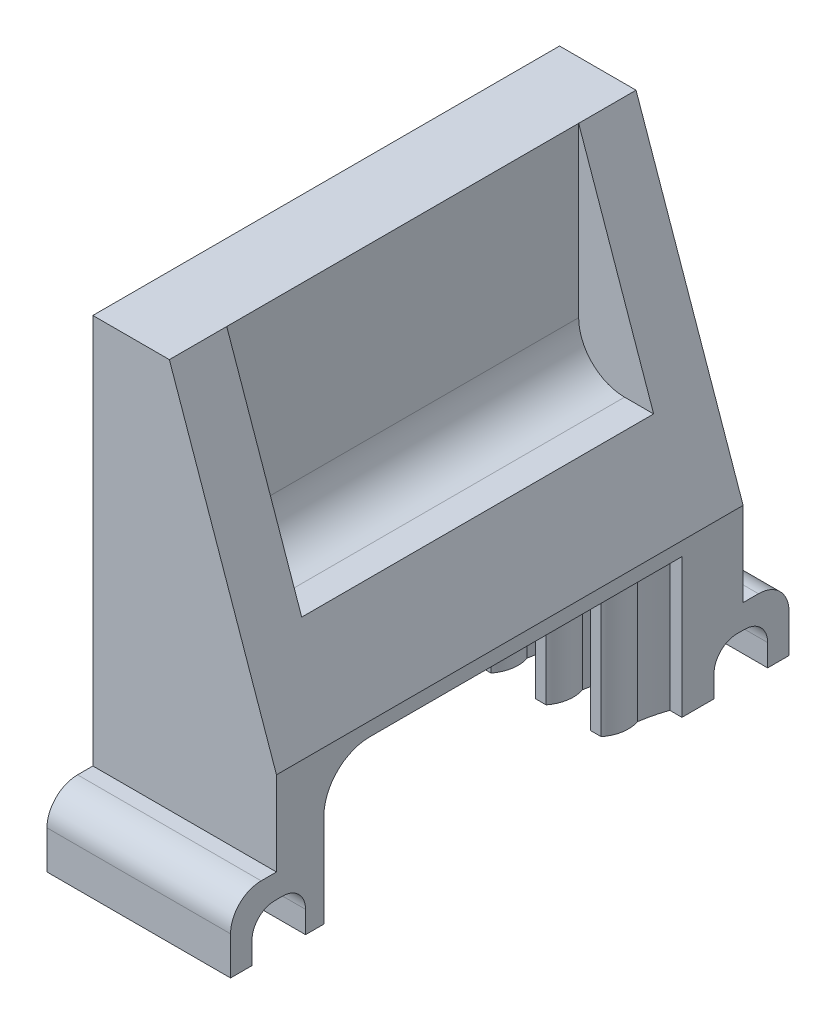
SolidWorks part; units mm, degrees
ref_plane "Front Plane" through (0, 0, 0) normal (0, 0, 1) x (1, 0, 0)
ref_plane "Top Plane" through (0, 0, 0) normal (0, 1, 0) x (1, 0, 0)
ref_plane "Right Plane" through (0, 0, 0) normal (1, 0, 0) x (0, 0, -1)
sketch "Sketch1" plane through (0, 0, 0) normal (0, 0, 1) x (1, 0, 0)
  line L0 (0, 0) -> (0, -30)
  line L1 (0, -30) -> (12, -30)
  line L2 (12, -30) -> (12, -20)
  line L3 (12, -20) -> (5, 0)
  line L4 (5, 0) -> (0, 0)
  dimension "D1" = 30
  dimension "D2" = 12
  dimension "D3" = 10
  dimension "D4" = 5
extrude "Boss-Extrude1" add sketch "Sketch1" against normal blind 30.5
sketch "Sketch4" plane through (0, 0, 0) normal (-1, 0, 0) x (0, 0, 1)
  line L0 (-30.5, 0) -> (-30.5, -30) construction
  line L1 (-26.5, -20.8999) -> (-3.1, -20.8999)
  line L2 (-26.5, -20.8999) -> (-26.5, -30.8999)
  line L3 (-26.5, -30.8999) -> (-3.1, -30.8999)
  line L4 (-3.1, -20.8999) -> (-3.1, -30.8999)
  point P4 (-26.5, -25.8999)
  dimension "D1" = 23.4
  dimension "D2" = 10
  dimension "D3" = 4
extrude "Cut-Extrude2" cut sketch "Sketch4" against normal blind 25 contours L2 L1 L4 L3
ref_plane "Plane1" through (0, 0, -15.25) normal (0, 0, 1) x (1, 0, 0)
sketch "Sketch6" plane through (0, 0, -15.25) normal (0, 0, 1) x (1, 0, 0)
  line L0 (5, 0) -> (5, -14)
  line L1 (5, -14) -> (9.9, -14)
  line L2 (12, -20) -> (5, 0) construction
  line L3 (9.9, -14) -> (5, 0)
  dimension "D1" = 14
extrude "Cut-Extrude4" cut sketch "Sketch6" against normal mid plane 23
ref_plane "Plane2" through (0, -26.4, 0) normal (0, 1, 0) x (1, 0, 0)
ref_plane "Plane3" through (0, -30, 0) normal (0, 1, 0) x (1, 0, 0)
sketch "Sketch7" plane through (0, -30, 0) normal (0, 1, 0) x (1, 0, 0)
  line L0 (11.2768, 28.75) -> (-19.7232, 28.75)
  line L62 (-6.6, 15.25) -> (6.6, 15.25) construction
  line L162 (11.2768, 28.75) -> (11.2768, 27.05)
  line L172 (-19.7232, 27.05) -> (-19.7232, 28.75)
  line L243 (11.2768, 27.05) -> (-19.7232, 27.05)
  dimension "D2" = 31
  dimension "D3" = 1.7
  dimension "D7" = 13.5
extrude "Boss-Extrude3" add sketch "Sketch7" along normal up to surface (9.1001 mm away) up to face at (6, -20.8999, -14.8)
sketch "Sketch10" plane through (0, -20.8999, 0) normal (0, 1, 0) x (1, 0, 0)
  line L1 (10.1114, 22.7678) -> (10.1114, 23.4692) construction
  line L2 (10.4547, 22.7678) -> (9.768, 22.7678)
  line L4 (-19.7232, 27.05) -> (0, 27.05) construction
  line L5 (8.8114, 27.05) -> (11.4114, 27.05)
  arc A0 (10.4547, 22.7678) -> (10.7888, 24.7989) centre (8.7521, 24.0909) ccw
  arc A1 (10.7888, 24.7989) -> (11.4114, 27.05) centre (20.4547, 23.3375) cw
  arc A2 (9.4339, 24.7989) -> (8.8114, 27.05) centre (-0.232, 23.3375) ccw
  arc A3 (9.768, 22.7678) -> (9.4339, 24.7989) centre (11.4706, 24.0909) cw
  dimension "D1" = 2.6
extrude "Boss-Extrude4" add sketch "Sketch10" against normal up to surface (9.1001 mm away) up to face at (6, -30, -1.55)
pattern_linear "LPattern1" count 8 spacing 3.6 along (-1, 0, 0) of "Boss-Extrude4"
sketch "Sketch11" plane through (0, 0, -30.5) normal (0, 0, -1) x (-1, 0, 0)
  line L0 (-12, -30) -> (-12, -20) construction
  line L1 (-12, -25.5) -> (0, -25.5)
  line L2 (-12, -25.5) -> (-12, -30)
  line L3 (-12, -30) -> (0, -30)
  line L4 (0, -25.5) -> (0, -30)
  dimension "D1" = 4.5
extrude "Boss-Extrude5" add sketch "Sketch11" along normal blind 3
fillet "Fillet1" radius 2 1 edges at (6, -25.5, -33.5)
mirror "Mirror1" about plane through (0, 0, -15.25) normal (0, 0, 1) of "Boss-Extrude5"
fillet "Fillet2" radius 2 1 edges at (6, -25.5, 3)
fillet "Fillet5" radius 3 2 edges at (5, -14, -15.25) (6, -20.8999, -3.1)
sketch "Sketch12" plane through (0, 0, 0) normal (-1, 0, 0) x (0, 0, 1)
  line L0 (-15.25, -20.6354) -> (-15.25, -36.9741) construction
  line L1 (-32.1, -27.0644) -> (-28.6, -27.0644)
  line L2 (-32.1, -27.0644) -> (-32.1, -30.5644)
  line L3 (-32.1, -30.5644) -> (-28.6, -30.5644)
  line L4 (-28.6, -27.0644) -> (-28.6, -30.5644)
  line L5 (-3.1, -30) -> (-3.1, -23.8999) construction
  line L11 (-15.25, -16.5) -> (-15.25, 16.5) construction
  line L12 (1.6, -30.5644) -> (-1.9, -30.5644)
  line L13 (-1.9, -27.0644) -> (-1.9, -30.5644)
  line L14 (1.6, -27.0644) -> (-1.9, -27.0644)
  line L15 (1.6, -27.0644) -> (1.6, -30.5644)
  dimension "D1" = 3.5
  dimension "D2" = 3.5
  dimension "D3" = 1.2
extrude "Cut-Extrude5" cut sketch "Sketch12" against normal up to surface (12 mm away) up to face at (12, -25.4167, -14.4786)
fillet "Fillet6" radius 1.5 4 edges at (6, -27.0644, -32.1) (6, -27.0644, -28.6) (6, -27.0644, 1.6) (6, -27.0644, -1.9)
